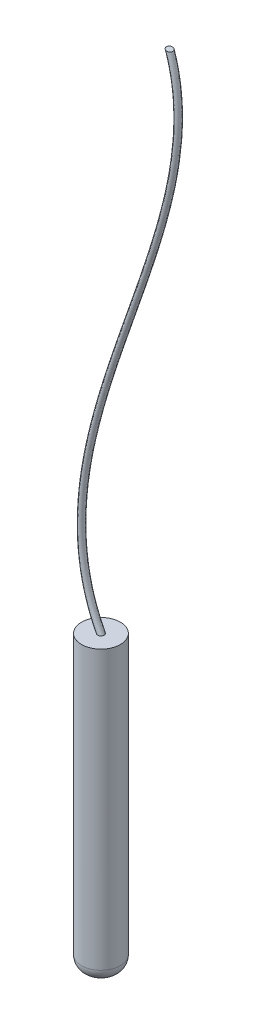
SolidWorks part; units mm, degrees
ref_plane "Ön Düzlem" through (0, 0, 0) normal (0, 0, 1) x (1, 0, 0)
ref_plane "Üst Düzlem" through (0, 0, 0) normal (0, 1, 0) x (1, 0, 0)
ref_plane "Sağ Düzlem" through (0, 0, 0) normal (1, 0, 0) x (0, 0, -1)
sketch "Çizim1" plane through (0, 0, 0) normal (0, 1, 0) x (1, 0, 0)
  circle A0 centre (0, 0) radius 3
  dimension "D1" = 6
extrude "Yükseklik-Ekstrüzyon1" add sketch "Çizim1" along normal blind 45
fillet "Fillet1" radius 2 1 edges at (0, 0, 3)
sketch "Sketch1" plane through (0, 45, 0) normal (0, 1, 0) x (1, 0, 0)
  circle A0 centre (0, 0) radius 0.5
  dimension "D1" = 1
sketch "Sketch2" plane through (0, 45, 0) normal (0, 1, 0) x (1, 0, 0)
  line L0 (0, 0) -> (2.1065, 0)
ref_plane "Plane1" through (0, 0, 0) normal (0, 0, 1) x (1, 0, 0)
sketch "Sketch3" plane through (0, 0, 0) normal (0, 0, 1) x (1, 0, 0)
  line L0 (0.5, 45) -> (-0.5, 45) construction
  spline S0 degree 3 poles (0, 45) (-12.4689, 68.7793) (18.5531, 105.5391) (10.62, 128.5359) knots 0 0 0 0 0.503588 0.503588 0.503588 0.503588
sweep "Sweep1" add profiles "Sketch1" path "Sketch3"
